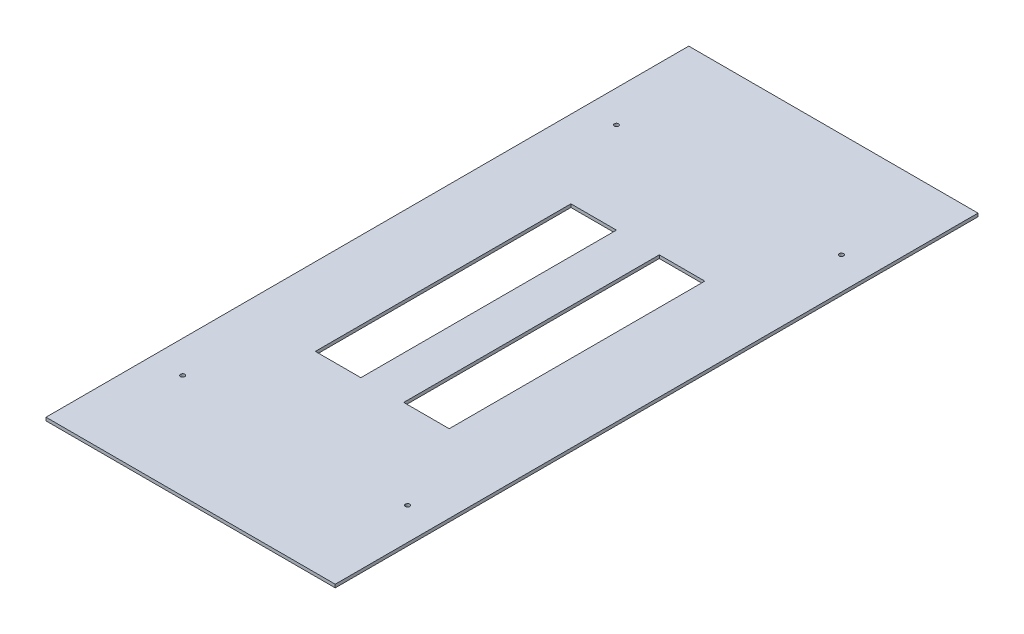
SolidWorks part; units mm, degrees
material "PA Type 6"
ref_plane "Front Plane" through (0, 0, 0) normal (0, 0, 1) x (1, 0, 0)
ref_plane "Top Plane" through (0, 0, 0) normal (0, 1, 0) x (1, 0, 0)
ref_plane "Right Plane" through (0, 0, 0) normal (1, 0, 0) x (0, 0, -1)
sketch "Sketch1" plane through (0, 0, 0) normal (0, 1, 0) x (1, 0, 0)
  line L0 (0, 212.5) -> (0, -212.5) construction
  line L1 (-115, 212.5) -> (115, 212.5)
  line L2 (-115, 212.5) -> (-115, -212.5)
  line L3 (-115, -212.5) -> (115, -212.5)
  line L4 (115, 212.5) -> (115, -212.5)
  line L5 (-115, 212.5) -> (115, -212.5) construction
  line L6 (-115, -212.5) -> (115, 212.5) construction
  line L8 (-115, 0) -> (115, 0) construction
  point P0 (0, 0)
  point P8 (-105, 202.5)
  point P14 (105, 202.5)
  point P16 (105, -202.5)
  point P17 (-105, -202.5)
  dimension "D1" = 210
  dimension "D2" = 405
  dimension "D3" = 10
  dimension "D4" = 10
extrude "Boss-Extrude1" add sketch "Sketch1" against normal blind 3 contours L1 L4 L3 L2
hole_wizard "Ø4.0 (4) Diameter Hole1" positions "Sketch2" profile "Sketch4" hole size "Ø4.0" standard "ANSI Metric" end condition through all
sketch "Sketch2" plane through (0, 0, 0) normal (0, 1, 0) x (1, 0, 0)
  point P0 (-105, 202.5)
  point P3 (105, 202.5)
  point P6 (105, -202.5)
  point P9 (-105, -202.5)
sketch "Sketch4" plane through (-105, 0, -202.5) normal (1, 0, 0) x (0, 0, 1)
  line L0 (0, 0) -> (0, 3)
  line L1 (0, 3) -> (2, 3)
  line L2 (2, 3) -> (2, 0)
  line L5 (2, 0) -> (0, 0)
  line L11 (0, -6.35) -> (0, 107.95) construction
  dimension "Thru Hole Dia." = 4
  dimension "Thru Hole Depth" = 3
sketch "Sketch5" plane through (0, 0, 0) normal (0, 1, 0) x (1, 0, 0)
  line L0 (0, 212.5) -> (0, -212.5) construction
  line L1 (-57.5, 112.5) -> (-25, 112.5) construction
  line L2 (-57.5, 112.5) -> (-57.5, -116.1) construction
  line L3 (-57.5, -116.1) -> (-25, -116.1) construction
  line L4 (-25, 112.5) -> (-25, -116.1) construction
  line L5 (25, 112.5) -> (25, -116.1) construction
  line L6 (-62.5, 117.5) -> (-20, 117.5)
  line L7 (-62.5, 117.5) -> (-62.5, -121.1)
  line L8 (-62.5, -121.1) -> (-20, -121.1)
  line L9 (-20, 117.5) -> (-20, -121.1)
  line L10 (57.5, -116.1) -> (25, -116.1) construction
  line L11 (57.5, 112.5) -> (57.5, -116.1) construction
  line L12 (57.5, 112.5) -> (25, 112.5) construction
  line L13 (20, 117.5) -> (20, -121.1)
  line L14 (62.5, -121.1) -> (20, -121.1)
  line L15 (62.5, 117.5) -> (62.5, -121.1)
  line L16 (62.5, 117.5) -> (20, 117.5)
  dimension "D1" = 90
  dimension "D2" = 228.6
  dimension "D3" = 57.5
  dimension "D4" = 5
  dimension "D5" = 5
  dimension "D6" = 5
  dimension "D7" = 5
  dimension "D8" = 25
extrude "Cut-Extrude1" cut sketch "Sketch5" against normal through all
sketch "Sketch6" plane through (0, 0, 0) normal (0, 1, 0) x (1, 0, 0)
  line L1 (-115, -212.5) -> (115, -212.5)
  line L2 (-115, -212.5) -> (-115, 212.5)
  line L3 (-115, 212.5) -> (115, 212.5)
  line L4 (115, -212.5) -> (115, 212.5)
  line L5 (-115, -212.5) -> (115, 212.5) construction
  line L6 (-115, 212.5) -> (115, -212.5) construction
  line L7 (-135, -300) -> (135, -300)
  line L8 (-135, -300) -> (-135, 300)
  line L9 (-135, 300) -> (135, 300)
  line L10 (135, -300) -> (135, 300)
  line L11 (-135, -300) -> (135, 300) construction
  line L12 (-135, 300) -> (135, -300) construction
  point P0 (0, 0)
  point P7 (0, 0)
  dimension "D1" = 270
  dimension "D2" = 600
extrude "Boss-Extrude3" add sketch "Sketch6" against normal up to surface (3 mm away) up to face at (-41.25, -3, 1.8)
